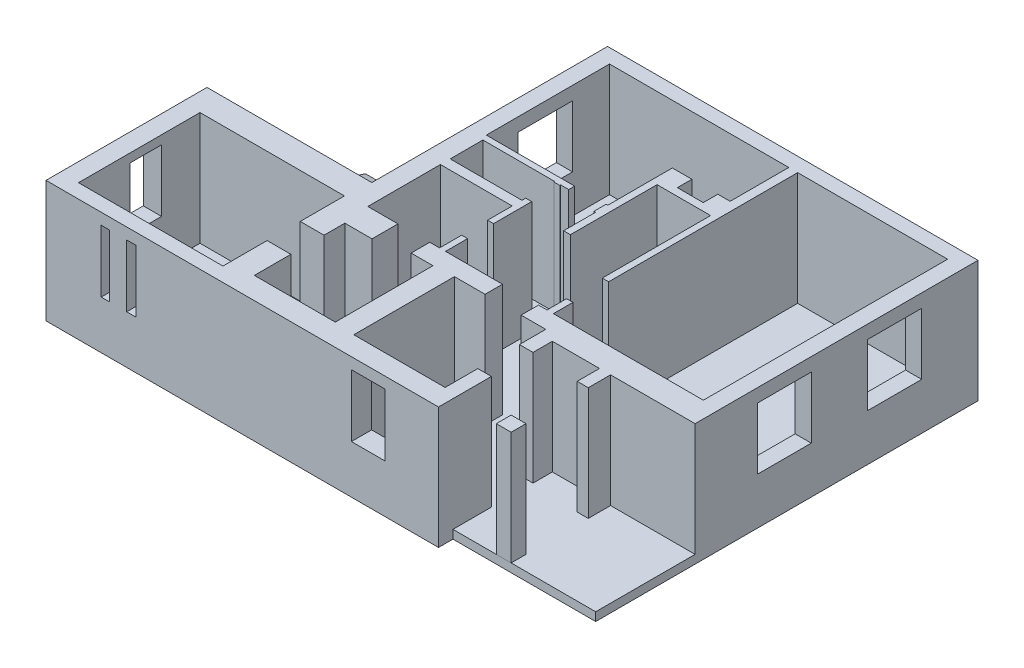
SolidWorks part; units mm, degrees
ref_plane "Спереди" through (0, 0, 0) normal (0, 0, 1) x (1, 0, 0)
ref_plane "Сверху" through (0, 0, 0) normal (0, 1, 0) x (1, 0, 0)
ref_plane "Справа" through (0, 0, 0) normal (1, 0, 0) x (0, 0, -1)
sketch "Эскиз1" plane through (0, 0, 0) normal (0, 1, 0) x (1, 0, 0)
  line L0 (0, 0) -> (4220, 0)
  line L1 (4220, 0) -> (4220, -1380)
  line L2 (4220, -1380) -> (3930, -1380)
  line L3 (3930, -1380) -> (3930, -1722.2944)
  line L4 (3320, -1722.2944) -> (3320, -1380)
  line L5 (3320, -1380) -> (2860, -1380)
  line L6 (2860, -1380) -> (2860, -2900)
  line L7 (2860, -2900) -> (2820, -2900)
  line L8 (0, -2900) -> (0, 0)
  line L9 (2820, -2900) -> (2820, -3185.6444)
  line L10 (2820, -3185.6444) -> (2860, -3185.6444)
  line L11 (2860, -3185.6444) -> (2860, -3940)
  line L12 (2080, -2900) -> (2080, -3040)
  line L13 (2080, -3040) -> (1890, -3040)
  line L14 (1890, -3040) -> (1890, -3060)
  line L15 (2080, -2900) -> (0, -2900)
  line L16 (3020, -3940) -> (3020, -1900.0287)
  line L17 (1890, -3060) -> (1750, -3060)
  line L18 (1750, -3060) -> (1750, -3040)
  line L19 (1750, -3040) -> (60, -3040)
  line L20 (60, -3040) -> (60, -3810)
  line L21 (60, -3810) -> (1750, -3810)
  line L22 (1750, -3810) -> (1750, -3720)
  line L23 (1750, -3720) -> (1890, -3720)
  line L24 (1890, -3720) -> (1890, -4620)
  line L25 (1890, -4620) -> (1750, -4620)
  line L26 (1750, -4620) -> (1750, -4040)
  line L27 (1750, -4040) -> (60, -4040)
  line L28 (60, -4040) -> (60, -5750)
  line L29 (60, -5750) -> (770, -5750)
  line L30 (770, -5750) -> (770, -6360)
  line L31 (770, -6360) -> (753.6696, -6360)
  line L32 (130, -6360) -> (130, -6850)
  line L33 (130, -6850) -> (-430, -6850)
  line L34 (-430, -6850) -> (-430, -5810)
  line L35 (-430, -5810) -> (-3830, -5810)
  line L36 (-3830, -5810) -> (-3830, -8670)
  line L37 (-3830, -8670) -> (-430, -8670)
  line L38 (-430, -8670) -> (-430, -7630)
  line L39 (-430, -7630) -> (130, -7630)
  line L40 (130, -7630) -> (130, -8490)
  line L41 (130, -8490) -> (2035, -8490)
  line L42 (2035, -8490) -> (2035, -6190)
  line L43 (2035, -6190) -> (1520, -6190)
  line L44 (1520, -6190) -> (1520, -5750)
  line L45 (1520, -5750) -> (1750, -5750)
  line L46 (1750, -5750) -> (1750, -5230)
  line L47 (1750, -5230) -> (1890, -5230)
  line L48 (1890, -5230) -> (1890, -5750)
  line L49 (1890, -5750) -> (3230, -5750)
  line L50 (3230, -5750) -> (3230, -6160)
  line L51 (3230, -6160) -> (2510, -6160)
  line L52 (2510, -6160) -> (2510, -8530)
  line L53 (2510, -8530) -> (4660, -8530)
  line L54 (4660, -8530) -> (4660, -7760)
  line L55 (4660, -7760) -> (4980, -7760)
  line L56 (2860, -3940) -> (3020, -3940)
  line L57 (4280, -1900.0287) -> (4280, -4450)
  line L58 (4280, -4450) -> (4430, -4450)
  line L59 (4430, -4450) -> (4430, 0)
  line L60 (4430, 0) -> (7960, 0)
  line L61 (7960, 0) -> (7960, -5750)
  line L62 (7960, -5750) -> (4430, -5750)
  line L63 (4430, -5750) -> (4430, -5290)
  line L64 (4430, -5290) -> (4280, -5290)
  line L65 (-4260, -5215) -> (-4260, -9005)
  line L66 (-2190, -5800.9457) -> (-2190, -8670) construction
  line L67 (4080, -6160) -> (4080, -5750)
  line L68 (4080, -5750) -> (4280, -5750)
  line L69 (4280, -5750) -> (4280, -5290)
  line L70 (4080, -6160) -> (4660, -6160)
  line L71 (4660, -6160) -> (4660, -6780)
  line L72 (4660, -6780) -> (4980, -6780)
  line L73 (753.6696, -6360) -> (130, -6360)
  line L74 (-217.7441, -870) -> (-217.7441, -2150) construction
  line L75 (8168.2501, -990) -> (8168.2501, -2270) construction
  line L76 (8168.2501, -3590) -> (8168.2501, -4860) construction
  line L77 (8249.589, -2900) -> (8168.2501, -2900) construction
  line L78 (8168.2501, -2900) -> (9306.9939, -2900) construction
  line L79 (8340, 335) -> (8340, -6325)
  line L80 (-380, 335) -> (-380, -3705)
  line L81 (2930, -8710.1469) -> (3720, -8710.1469) construction
  line L82 (-380, -3705) -> (-2040, -3705)
  line L83 (-4260, -9005) -> (4980, -9005)
  line L84 (-380, 335) -> (8340, 335)
  line L85 (0, 0) -> (-380, 0) construction
  line L86 (7960, 0) -> (8340, 0) construction
  line L87 (-2040, -3705) -> (-2040, -5215)
  line L88 (-2040, -5215) -> (-4260, -5215)
  line L90 (-430, -8670) -> (-430, -9005) construction
  line L91 (7960, 0) -> (7960, 335) construction
  line L92 (3320, -1722.2944) -> (3930, -1722.2944)
  line L93 (3020, -1900.0287) -> (4280, -1900.0287)
  line L94 (4980, -9005) -> (4980, -7760)
  line L95 (4980, -6325) -> (4980, -6780)
  line L96 (6000, -8315) -> (6000, -8665)
  line L97 (8340, -6325) -> (6350, -6325)
  line L98 (6000, -8665) -> (6350, -8665)
  line L99 (6350, -8665) -> (6350, -8315)
  line L100 (6350, -8315) -> (6000, -8315)
  line L101 (6090, -6325) -> (6090, -6850)
  line L102 (6090, -6850) -> (6350, -6850)
  line L103 (6350, -6850) -> (6350, -6325)
  line L105 (6090, -6325) -> (4980, -6325)
  point P92 (761.8348, -6360)
  dimension "D1" = 4220
  dimension "D2" = 2900
  dimension "D3" = 1380
  dimension "D4" = 1360
  dimension "D5" = 290
  dimension "D6" = 900
  dimension "D7" = 40
  dimension "D8" = 780
  dimension "D9" = 970
  dimension "D10" = 1130
  dimension "D11" = 140
  dimension "D12" = 770
  dimension "D13" = 1690
  dimension "D14" = 1830
  dimension "D15" = 20
  dimension "D16" = 680
  dimension "D17" = 410
  dimension "D18" = 2190
  dimension "D19" = 580
  dimension "D21" = 1710
  dimension "D22" = 710
  dimension "D23" = 1460
  dimension "D24" = 2390
  dimension "D25" = 2190
  dimension "D26" = 1340
  dimension "D27" = 460
  dimension "D28" = 1300
  dimension "D29" = 3940
  dimension "D30" = 5750
  dimension "D31" = 620
  dimension "D32" = 1600
  dimension "D33" = 380
  dimension "D34" = 350
  dimension "D35" = 2150
  dimension "D36" = 2370
  dimension "D37" = 150
  dimension "D38" = 1990
  dimension "D39" = 1040
  dimension "D40" = 8720
  dimension "D41" = 6070
  dimension "D42" = 870
  dimension "D43" = 2150
  dimension "D44" = 890
  dimension "D45" = 2160
  dimension "D46" = 3480
  dimension "D47" = 4760
  dimension "D48" = 2850
  dimension "D49" = 9340
  dimension "D50" = 1660
  dimension "D51" = 2130
  dimension "D52" = 2740
  dimension "D53" = 490
  dimension "D54" = 1270
  dimension "D55" = 3960
  dimension "D56" = 640
  dimension "D57" = 1265
  dimension "D58" = 440
  dimension "D59" = 3400
  dimension "D60" = 1040
  dimension "D61" = 1760
  dimension "D62" = 940
  dimension "D63" = 1730
  dimension "D64" = 1510
  dimension "D65" = 335
  dimension "D66" = 4040
  dimension "D67" = 3360
  dimension "D68" = 2680
  dimension "D69" = 260
  dimension "D70" = 525
  dimension "D71" = 340
  dimension "D72" = 9240
extrude "Бобышка-Вытянуть1" add sketch "Эскиз1" along normal blind 2665
sketch "Эскиз2" plane through (0, 0, 0) normal (0, -1, 0) x (1, 0, 0)
  line L0 (-4260, 5215) -> (-4260, 9005) construction
  line L1 (-2040, 5215) -> (-4260, 5215) construction
  line L2 (-2040, 3705) -> (-2040, 5215) construction
  line L3 (-380, 3705) -> (-2040, 3705) construction
  line L4 (-380, -335) -> (-380, 3705) construction
  line L5 (8340, -335) -> (-380, -335) construction
  line L7 (-4260, 9005) -> (4980, 9005) construction
  line L8 (-4260, 5215) -> (-4260, 9005)
  line L9 (-2040, 5215) -> (-4260, 5215)
  line L10 (-2040, 3705) -> (-2040, 5215)
  line L11 (-380, 3705) -> (-2040, 3705)
  line L12 (-380, -335) -> (-380, 3705)
  line L13 (8340, -335) -> (-380, -335)
  line L15 (-4260, 9005) -> (4980, 9005)
  line L16 (8340, 6325) -> (8340, -335) construction
  line L17 (8340, 8665) -> (8340, -335)
  line L18 (6000, 8665) -> (6350, 8665) construction
  line L19 (4980, 8665) -> (8340, 8665)
  line L20 (4980, 9005) -> (4980, 7760) construction
  line L21 (4980, 9005) -> (4980, 8665)
extrude "Бобышка-Вытянуть2" add sketch "Эскиз2" along normal blind 200
sketch "Эскиз3" plane through (8340, 0, 0) normal (1, 0, 0) x (0, 0, -1)
  line L0 (-5750, 2665) -> (-5750, 0) construction
  line L1 (-4860, 900) -> (-3590, 900)
  line L2 (-4860, 900) -> (-4860, 2350)
  line L3 (-4860, 2350) -> (-3590, 2350)
  line L4 (-3590, 900) -> (-3590, 2350)
  line L5 (-2270, 900) -> (-990, 900)
  line L6 (-2270, 900) -> (-2270, 2350)
  line L7 (-2270, 2350) -> (-990, 2350)
  line L8 (-990, 900) -> (-990, 2350)
  line L9 (0, 0) -> (-4450, 0) construction
  dimension "D1" = 890
  dimension "D2" = 2160
  dimension "D3" = 3480
  dimension "D4" = 4760
  dimension "D5" = 900
  dimension "D6" = 1450
extrude "Вырез-Вытянуть1" cut sketch "Эскиз3" against normal up to surface (380 mm away) up to face at (7960, 1332.5, 2875)
sketch "Эскиз4" plane through (-380, 0, 0) normal (-1, 0, 0) x (0, 0, 1)
  line L0 (1380, 0) -> (0, 0) construction
  line L1 (870, 2350) -> (2150, 2350)
  line L2 (870, 2350) -> (870, 900)
  line L3 (870, 900) -> (2150, 900)
  line L4 (2150, 2350) -> (2150, 900)
  line L5 (0, 2665) -> (0, 0) construction
  dimension "D1" = 900
  dimension "D2" = 1450
  dimension "D3" = 870
  dimension "D4" = 2150
extrude "Вырез-Вытянуть2" cut sketch "Эскиз4" against normal up to next (380 mm away)
sketch "Эскиз5" plane through (-4260, 0, 0) normal (-1, 0, 0) x (0, 0, 1)
  line L0 (8670, 0) -> (7630, 0) construction
  line L1 (6715, 1000) -> (7455, 1000)
  line L2 (6715, 1000) -> (6715, 2460)
  line L3 (6715, 2460) -> (7455, 2460)
  line L4 (7455, 1000) -> (7455, 2460)
  line L5 (5215, 2665) -> (5215, -200) construction
  line L6 (9005, 2665) -> (9005, -200) construction
  dimension "D1" = 1000
  dimension "D2" = 1460
  dimension "D3" = 1500
  dimension "D4" = 1550
extrude "Вырез-Вытянуть3" cut sketch "Эскиз5" against normal up to next (430 mm away)
sketch "Эскиз6" plane through (0, 0, 9005) normal (0, 0, 1) x (1, 0, 0)
  line L0 (4660, 2665) -> (4660, 0) construction
  line L1 (2930, 935) -> (3720, 935)
  line L2 (2930, 935) -> (2930, 2400)
  line L3 (2930, 2400) -> (3720, 2400)
  line L4 (3720, 935) -> (3720, 2400)
  line L5 (4660, 0) -> (4080, 0) construction
  line L6 (-4260, 2665) -> (-4260, -200) construction
  line L7 (-2960, 935) -> (-2760, 935)
  line L8 (-2960, 935) -> (-2960, 2400)
  line L9 (-2960, 2400) -> (-2760, 2400)
  line L10 (-2760, 935) -> (-2760, 2400)
  line L11 (-2360, 935) -> (-2140, 935)
  line L12 (-2360, 935) -> (-2360, 2400)
  line L13 (-2360, 2400) -> (-2140, 2400)
  line L14 (-2140, 935) -> (-2140, 2400)
  dimension "D1" = 940
  dimension "D2" = 1730
  dimension "D3" = 935
  dimension "D4" = 1465
  dimension "D5" = 1300
  dimension "D6" = 1500
  dimension "D7" = 1900
  dimension "D8" = 2120
extrude "Вырез-Вытянуть4" cut sketch "Эскиз6" against normal up to next (475 mm away)
sketch "Эскиз8" plane through (-2040, 0, 0) normal (-1, 0, 0) x (0, 0, 1)
  line L0 (5215, 2665) -> (5215, -200) construction
  line L1 (5215, 1750) -> (3705, 1260)
  line L2 (5215, 1750) -> (5215, 2665)
  line L3 (5215, 2665) -> (3705, 2665)
  line L4 (3705, 1260) -> (3705, 2665)
  line L5 (3705, 2665) -> (3705, -200) construction
  dimension "D1" = 1460
  dimension "D2" = 1950
extrude "Вырез-Вытянуть5" cut sketch "Эскиз8" against normal up to surface (1660 mm away) up to face at (-380, 1625, 1510)
sketch "Эскиз9" plane through (-2040, 0, 0) normal (-1, 0, 0) x (0, 0, 1)
  line L0 (5215, -200) -> (3705, -200) construction
  line L1 (4225, -200) -> (5145, -200)
  line L2 (4225, -200) -> (4225, 1050)
  line L3 (4225, 1050) -> (5145, 1050)
  line L4 (5145, -200) -> (5145, 1050)
  line L5 (5215, 1750) -> (5215, -200) construction
  dimension "D1" = 70
  dimension "D2" = 990
  dimension "D3" = 1250
extrude "Вырез-Вытянуть6" cut sketch "Эскиз9" against normal blind 300
